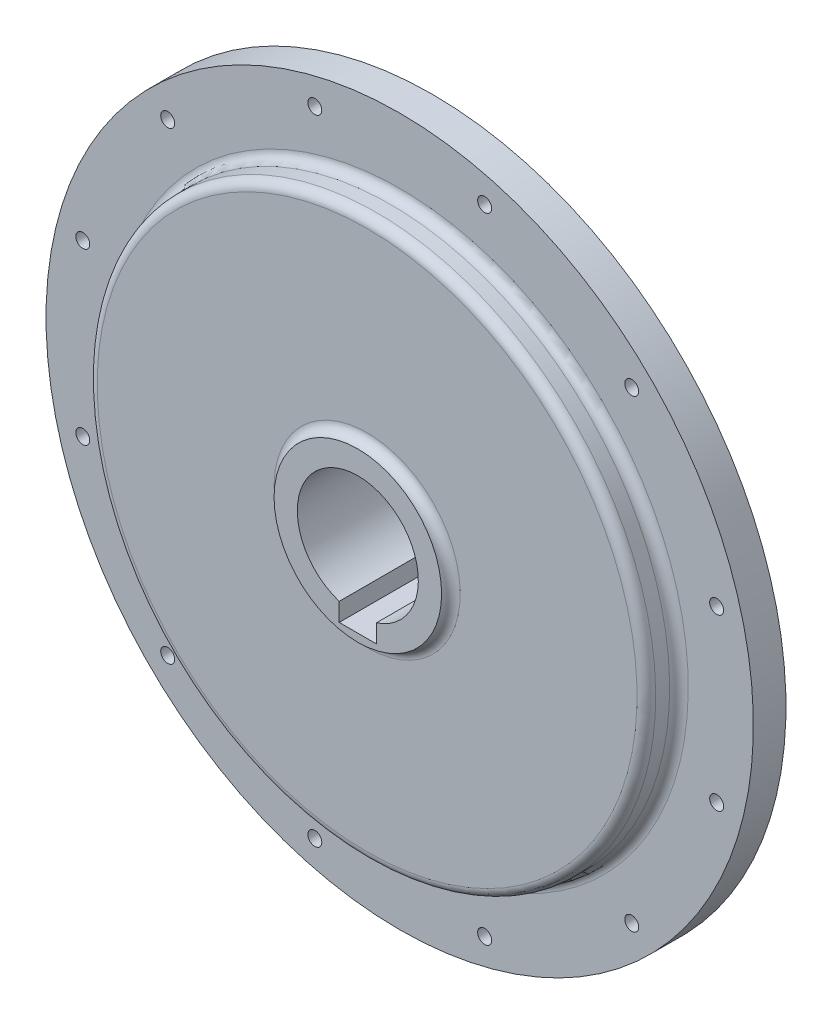
SolidWorks part; units mm, degrees
ref_plane "Front Plane" through (0, 0, 0) normal (0, 0, 1) x (1, 0, 0)
ref_plane "Top Plane" through (0, 0, 0) normal (0, 1, 0) x (1, 0, 0)
ref_plane "Right Plane" through (0, 0, 0) normal (1, 0, 0) x (0, 0, -1)
sketch "Sketch1" plane through (0, 0, 0) normal (1, 0, 0) x (0, 0, -1)
  line L0 (0, 0) -> (-21, 0) construction
  line L1 (0, 13) -> (-21, 13)
  line L2 (-21, 13) -> (-21, 18)
  line L3 (-21, 18) -> (-19, 18)
  line L4 (-19, 18) -> (-19, 60)
  line L5 (-19, 60) -> (-12, 60)
  line L6 (-12, 60) -> (-12, 76)
  line L7 (-12, 76) -> (-5, 76)
  line L8 (-5, 76) -> (-5, 63)
  line L9 (-5, 63) -> (-3, 63)
  line L10 (-3, 63) -> (-3, 50)
  line L11 (-3, 50) -> (-7, 50)
  line L12 (-7, 50) -> (-7, 18)
  line L13 (-7, 18) -> (0, 18)
  line L14 (0, 18) -> (0, 13)
  line L15 (0, 0) -> (-72.5762, 0) construction
  dimension "D1" = 21
  dimension "D2" = 13
  dimension "D3" = 18
  dimension "D4" = 2
  dimension "D5" = 12
  dimension "D6" = 3
  dimension "D7" = 120
  dimension "D8" = 50
  dimension "D9" = 76
  dimension "D10" = 2
  dimension "D11" = 7
  dimension "D12" = 63
revolve "Revolve1" add sketch "Sketch1" angle 360 about L0
fillet "Fillet1" radius 2 5 edges at (0, 18, 7) (0, 50, 7) (0, 60, 12) (0, 60, 19) (0, 18, 19)
sketch "Sketch3" plane through (0, 0, 5) normal (0, 0, -1) x (-1, 0, 0)
  circle A0 centre (0, 0) radius 67
  circle A1 centre (0, 0) radius 65
  dimension "D1" = 2
  dimension "D2" = 134
extrude "Cut-Extrude1" cut sketch "Sketch3" against normal blind 3
sketch "Sketch4" plane through (0, 0, 12) normal (0, 0, 1) x (1, 0, 0)
  line L0 (0, 0) -> (0, 80.0903) construction
  line L1 (0, 0) -> (20.8179, 77.6933) construction
  arc A0 (18.2487, 68.1053) -> (28.3714, 64.5477) centre (0, 0) cw construction
  circle A1 centre (18.2487, 68.1053) radius 1.5
  dimension "D2" = 3
  dimension "D1" = 15
extrude "Cut-Extrude3" cut sketch "Sketch4" against normal through all
pattern_circular "CirPattern1" count 12 over 360 about axis through (0, 0, 0) along (0, 0, 1) of "Cut-Extrude3"
sketch "Sketch5" plane through (0, 0, 21) normal (0, 0, 1) x (1, 0, 0)
  line L0 (4, -9.3) -> (4, -16.3)
  line L1 (-4, -9.3) -> (4, -9.3)
  line L2 (-4, -9.3) -> (-4, -16.3)
  line L3 (-4, -16.3) -> (4, -16.3)
  line L4 (0, -13) -> (0, -16.3) construction
  circle A0 centre (0, 0) radius 13 construction
  dimension "D3" = 3.3
  dimension "D1" = 8
  dimension "D2" = 7
extrude "Cut-Extrude4" cut sketch "Sketch5" against normal through all
